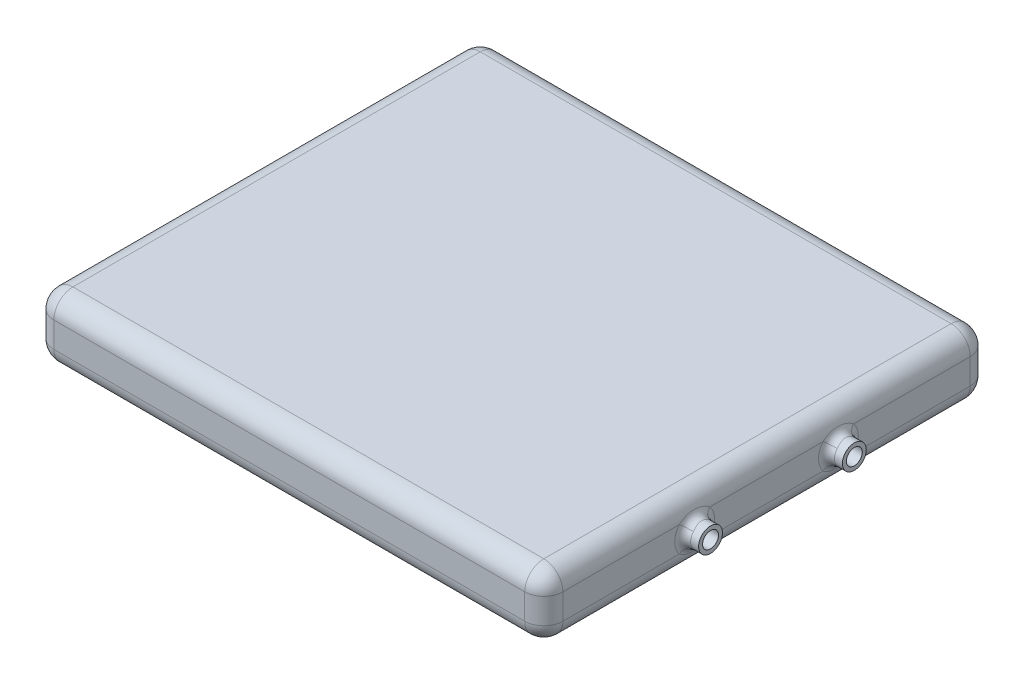
SolidWorks part; units mm, degrees
material "Acrylic (Medium-high impact)"
ref_plane "Front" through (0, 0, 0) normal (0, 0, 1) x (1, 0, 0)
ref_plane "Top" through (0, 0, 0) normal (0, 1, 0) x (1, 0, 0)
ref_plane "Right" through (0, 0, 0) normal (1, 0, 0) x (0, 0, -1)
sketch "Sketch1" plane through (0, 0, 0) normal (0, 1, 0) x (1, 0, 0)
  line L1 (0, 0) -> (406.4, 0)
  line L2 (0, 0) -> (0, 355.6)
  line L3 (0, 355.6) -> (406.4, 355.6)
  line L4 (406.4, 0) -> (406.4, 355.6)
  dimension "D1" = 355.6
  dimension "D2" = 406.4
extrude "Boss-Extrude1" add sketch "Sketch1" along normal blind 50.8
sketch "Sketch2" plane through (406.4, 0, 0) normal (1, 0, 0) x (0, 0, -1)
  line L0 (177.8, 0) -> (177.8, 50.8) construction
  line L1 (0, 0) -> (355.6, 0) construction
  line L2 (0, 50.8) -> (355.6, 50.8) construction
  line L3 (177.8, 25.4) -> (120.3951, 25.4) construction
  line L4 (177.8, 25.4) -> (235.2049, 25.4) construction
  circle A0 centre (120.3951, 25.4) radius 6.35
  circle A1 centre (235.2049, 25.4) radius 6.35
  circle A2 centre (120.3951, 25.4) radius 9.525
  circle A3 centre (235.2049, 25.4) radius 9.525
  dimension "D1" = 12.7
  dimension "D3" = 19.05
  dimension "D2" = 57.4049
extrude "Boss-Extrude2" add sketch "Sketch2" along normal blind 12.7
fillet "Fillet1" radius 15.24 12 edges at (406.4, 25.4, -355.6) (406.4, 0, -177.8) (203.2, 0, -355.6) (0, 25.4, -355.6) (0, 0, -177.8) (0, 25.4, 0) (406.4, 25.4, 0) (203.2, 0, 0) (203.2, 50.8, -355.6) (406.4, 50.8, -177.8) (203.2, 50.8, 0) (0, 50.8, -177.8)
fillet "Fillet2" radius 6.35 2 edges at (406.4, 25.4, -110.8701) (406.4, 25.4, -225.6799)
shell "Shell1" thickness 1.524
